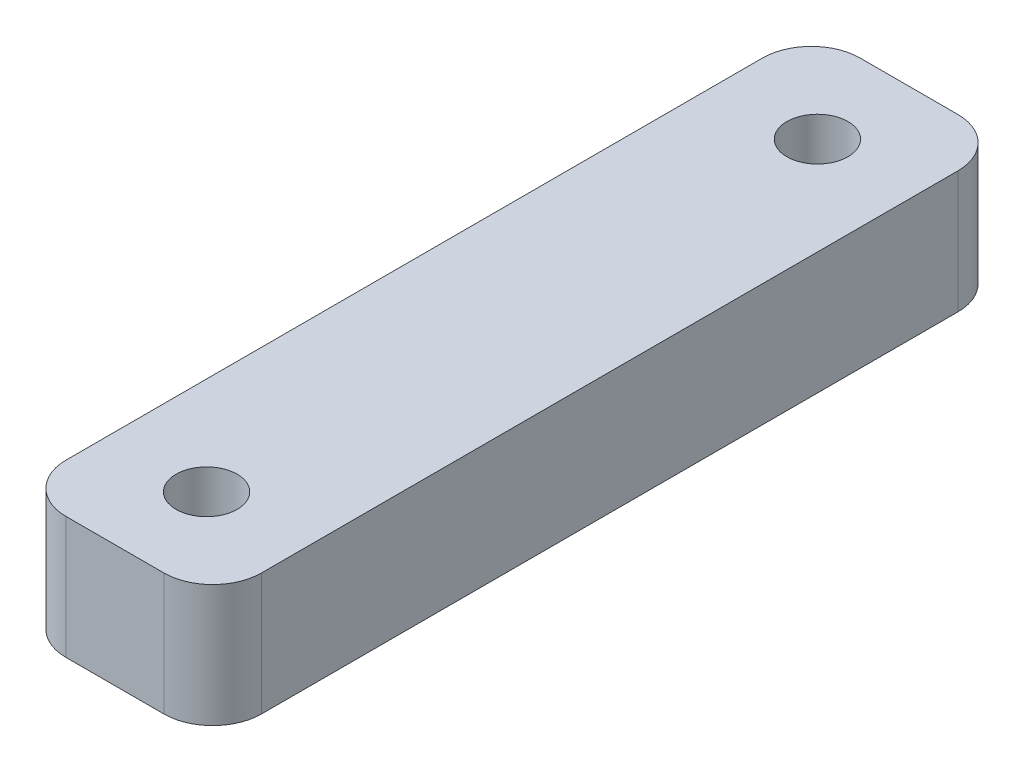
SolidWorks part; units mm, degrees
material "PE haute densité"
ref_plane "Plan de face" through (0, 0, 0) normal (0, 0, 1) x (1, 0, 0)
ref_plane "Plan de dessus" through (0, 0, 0) normal (0, 1, 0) x (1, 0, 0)
ref_plane "Plan de droite" through (0, 0, 0) normal (1, 0, 0) x (0, 0, -1)
sketch "Esquisse1" plane through (0, 0, 0) normal (0, 0, 1) x (1, 0, 0)
  line L1 (-8, -5) -> (8, -5)
  line L2 (-8, -5) -> (-8, 5)
  line L3 (-8, 5) -> (8, 5)
  line L4 (8, -5) -> (8, 5)
  line L5 (-8, -5) -> (8, 5) construction
  line L6 (-8, 5) -> (8, -5) construction
  point P0 (0, 0)
  dimension "D1" = 16
  dimension "D2" = 10
extrude "Boss.-Extru.1" add sketch "Esquisse1" along normal blind 65
sketch "Esquisse2" plane through (0, 5, 0) normal (0, 1, 0) x (1, 0, 0)
  line L0 (-8, -32.5) -> (8, -32.5) construction
  line L1 (-8, -65) -> (-8, 0) construction
  line L2 (8, -65) -> (8, 0) construction
  circle A0 centre (0, -7.5) radius 2.5
  circle A1 centre (0, -57.5) radius 2.5
  dimension "D1" = 5
  dimension "D2" = 50
extrude "Enlèv. mat.-Extru.1" cut sketch "Esquisse2" against normal through all
fillet "Congé1" radius 4 4 edges at (-8, 0, 0) (-8, 0, 65) (8, 0, 65) (8, 0, 0)
sketch "Esquisse3" plane through (0, 5, 0) normal (0, 1, 0) x (1, 0, 0)
  line L4 (4, 0) -> (-4, 0)
  line L5 (-8, -4) -> (-8, -61)
  line L6 (-4, -65) -> (4, -65)
  line L7 (8, -61) -> (8, -4)
  line L8 (4, 0) -> (-4, 0)
  line L9 (-8, -4) -> (-8, -61)
  line L10 (-4, -65) -> (4, -65)
  line L11 (8, -61) -> (8, -4)
  arc A4 (-4, 0) -> (-8, -4) centre (-4, -4) ccw
  arc A5 (-8, -61) -> (-4, -65) centre (-4, -61) ccw
  arc A6 (4, -65) -> (8, -61) centre (4, -61) ccw
  arc A7 (8, -4) -> (4, 0) centre (4, -4) ccw
  arc A8 (-4, 0) -> (-8, -4) centre (-4, -4) ccw
  arc A9 (-8, -61) -> (-4, -65) centre (-4, -61) ccw
  arc A10 (4, -65) -> (8, -61) centre (4, -61) ccw
  arc A11 (8, -4) -> (4, 0) centre (4, -4) ccw
  dimension "D1" = 0
extrude "Boss.-Extru.2" [suppressed] add sketch "Esquisse3" against normal blind 0.2
